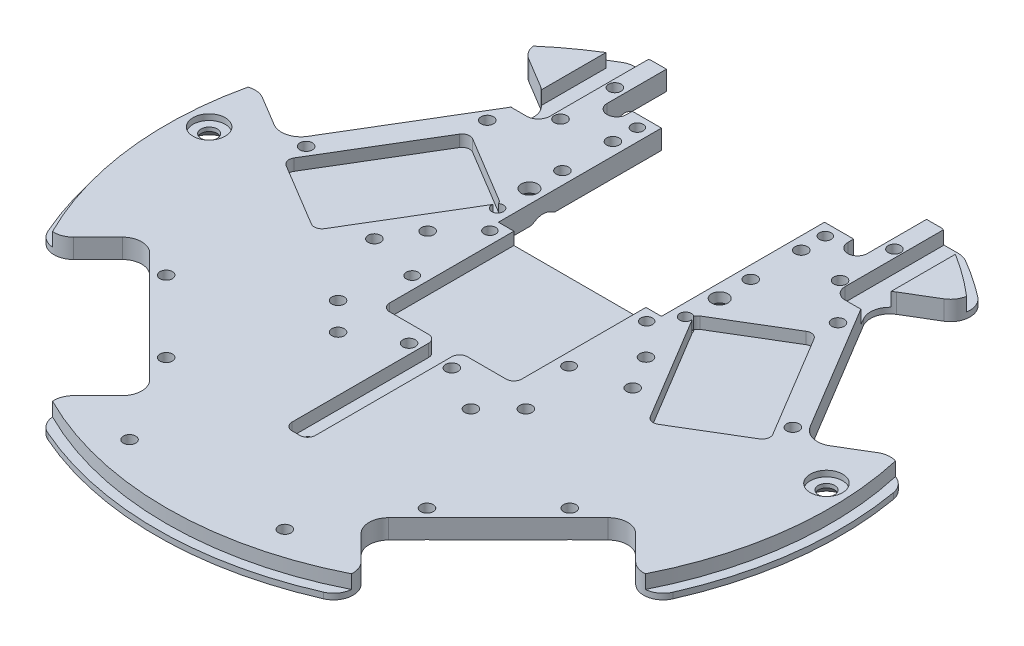
SolidWorks part; units mm, degrees
material "7079 Alloy"
ref_plane "Front" through (0, 0, 0) normal (0, 0, 1) x (1, 0, 0)
ref_plane "Top" through (0, 0, 0) normal (0, 1, 0) x (1, 0, 0)
ref_plane "Right" through (0, 0, 0) normal (1, 0, 0) x (0, 0, -1)
sketch "Sketch1" plane through (0, 0, 0) normal (0, 1, 0) x (1, 0, 0)
  line L0 (0, 0) -> (88, 0)
  line L1 (0, 88) -> (0, 0)
  line L2 (-88, 0) -> (0, 0)
  line L3 (0, -88) -> (0, 0)
  line L4 (0, 0) -> (62.2254, -62.2254)
  line L5 (0, 0) -> (-62.2254, -62.2254)
  line L6 (0, 0) -> (75.4307, 45.3234)
  line L7 (0, 0) -> (-75.4307, 45.3234)
  line L8 (59.4468, 64.8851) -> (41.5542, 54.1341)
  line L9 (41.5542, 54.1341) -> (67.3061, 11.2757)
  line L10 (67.3061, 11.2757) -> (85.1987, 22.0267)
  line L11 (77.3392, -41.9839) -> (62.579, -27.2236)
  line L12 (62.579, -27.2236) -> (27.2236, -62.579)
  line L13 (27.2236, -62.579) -> (41.9839, -77.3392)
  line L14 (-41.9839, -77.3392) -> (-27.2236, -62.579)
  line L15 (-27.2236, -62.579) -> (-62.579, -27.2236)
  line L16 (-62.579, -27.2236) -> (-77.3392, -41.9839)
  line L17 (-85.1987, 22.0267) -> (-67.3061, 11.2757)
  line L18 (-67.3061, 11.2757) -> (-41.5542, 54.1341)
  line L19 (-41.5542, 54.1341) -> (-59.4468, 64.8851)
  line L20 (-59.4468, 64.8851) -> (7.3885, 64.8851)
  line L21 (7.3885, 64.8851) -> (59.4468, 64.8851)
  line L22 (-41.5542, 54.1341) -> (0, 54.1341)
  line L23 (0, 54.1341) -> (41.5542, 54.1341)
  line L24 (41.5542, 54.1341) -> (41.5542, 77.5709)
  line L25 (-41.5542, 77.5709) -> (0, 77.5709)
  line L26 (-41.5542, 77.5709) -> (-41.5542, 54.1341)
  line L27 (0, 77.5709) -> (41.5542, 77.5709)
  circle A0 centre (0, 0) radius 88
  dimension "D1" = 176
  dimension "D2" = 31
  dimension "D3" = 31
  dimension "D4" = 45
  dimension "D5" = 24.5
  dimension "D6" = 24.5
  dimension "D7" = 24.5
  dimension "D8" = 24.5
  dimension "D9" = 25
  dimension "D10" = 25
  dimension "D11" = 25
  dimension "D12" = 25
  dimension "D13" = 25
  dimension "D14" = 25
  dimension "D15" = 25
  dimension "D16" = 25
sketch "Sketch2" plane through (0, 0, 0) normal (0, 1, 0) x (1, 0, 0)
  line L0 (85.1987, 22.0267) -> (67.3061, 11.2757)
  line L1 (67.3061, 11.2757) -> (41.5542, 54.1341)
  line L2 (77.3392, -41.9839) -> (62.579, -27.2236)
  line L3 (62.579, -27.2236) -> (27.2236, -62.579)
  line L4 (27.2236, -62.579) -> (41.9839, -77.3392)
  line L5 (-41.9839, -77.3392) -> (-27.2236, -62.579)
  line L6 (-27.2236, -62.579) -> (-62.579, -27.2236)
  line L7 (-62.579, -27.2236) -> (-77.3392, -41.9839)
  line L8 (-85.1987, 22.0267) -> (-67.3061, 11.2757)
  line L9 (-67.3061, 11.2757) -> (-41.5542, 54.1341)
  line L10 (-43, 76.7789) -> (43, 76.7789)
  line L15 (-41.5542, 54.1341) -> (-59.4468, 64.8851)
  line L16 (0, 0) -> (0, 111.6496) construction
  line L17 (41.5542, 54.1341) -> (59.4468, 64.8851)
  line L18 (-43, 76.7789) -> (43, 76.7789) construction
  arc A0 (85.1987, 22.0267) -> (77.3392, -41.9839) centre (0, 0) cw
  arc A1 (41.9839, -77.3392) -> (-41.9839, -77.3392) centre (0, 0) cw
  arc A2 (-77.3392, -41.9839) -> (-85.1987, 22.0267) centre (0, 0) cw
  arc A3 (-43, 76.7789) -> (-59.4468, 64.8851) centre (0, 0) ccw
  arc A4 (59.4468, 64.8851) -> (43, 76.7789) centre (0, 0) ccw
  dimension "D2" = 86
extrude "Extrude1" add sketch "Sketch2" against normal blind 5
sketch "Sketch3" plane through (0, 0, 0) normal (0, 1, 0) x (1, 0, 0)
  line L0 (-21, 76.7789) -> (-21, 21)
  line L1 (-21, 21) -> (21, 21)
  line L2 (21, 21) -> (21, 76.7789)
  line L3 (43, 76.7789) -> (-43, 76.7789) construction
  line L5 (-21, 76.7789) -> (21, 76.7789)
  dimension "D1" = 21
  dimension "D2" = 21
  dimension "D3" = 21
extrude "Extrude2" cut sketch "Sketch3" against normal up to surface (5 mm away) up to face at (0, -5, -1.5971)
sketch "Sketch4" plane through (0, 0, 0) normal (0, 1, 0) x (-1, 0, 0)
  line L0 (17, 13) -> (17, -27)
  line L1 (-3, 13) -> (-3, 52.119)
  line L2 (17, 13) -> (3, 13)
  line L3 (17, -27) -> (-17, -27)
  line L4 (-17, -27) -> (-17, 13)
  line L5 (21, -21) -> (-21, -21) construction
  line L6 (-3, 52.119) -> (3, 52.119)
  line L7 (3, 52.119) -> (3, 13)
  line L9 (-3, 13) -> (-17, 13)
  dimension "D1" = 34
  dimension "D2" = 17
  dimension "D3" = 34
  dimension "D4" = 40
  dimension "D5" = 6
  dimension "D6" = 14
extrude "Extrude3" cut sketch "Sketch4" against normal blind 3.2
sketch "Sketch5" plane through (0, 0, 0) normal (0, 1, 0) x (1, 0, 0)
  line L0 (42.9633, -4.5175) -> (62.6781, 7.3283)
  line L1 (62.6781, 7.3283) -> (44.6518, 37.3292)
  line L2 (44.6518, 37.3292) -> (24.9369, 25.4833)
  line L3 (24.9369, 25.4833) -> (42.9633, -4.5175)
  line L5 (67.3061, 11.2757) -> (41.5542, 54.1341) construction
  line L6 (85.1987, 22.0267) -> (67.3061, 11.2757) construction
  dimension "D1" = 6
  dimension "D2" = 35
  dimension "D3" = 23
  dimension "D4" = 1
extrude "Extrude4" cut sketch "Sketch5" against normal blind 3
mirror "Mirror1" about plane through (0, 0, 0) normal (1, 0, 0) of "Extrude4"
sketch "Sketch6" plane through (0, 0, 0) normal (0, 1, 0) x (1, 0, 0)
  line L0 (0, 0) -> (75.4307, 45.3234) construction
  line L1 (41.5542, 54.1341) -> (67.3061, 11.2757) construction
  line L2 (62.579, -27.2236) -> (27.2236, -62.579) construction
  line L3 (0, 0) -> (62.2254, -62.2254) construction
  circle A0 centre (45.1631, 42.303) radius 1.6
  circle A1 centre (62.6744, 13.1593) radius 1.6
  circle A2 centre (51.9723, -33.5876) radius 1.6
  circle A3 centre (33.5876, -51.9723) radius 1.6
  dimension "D1" = 3.2
  dimension "D2" = 3.2
  dimension "D3" = 3.2
  dimension "D4" = 3.2
  dimension "D6" = 3
  dimension "D8" = 3
  dimension "D9" = 3
  dimension "D10" = 13
  dimension "D11" = 13
  dimension "D12" = 3
  dimension "D5" = 13
  dimension "D7" = 21
extrude "Extrude5" cut sketch "Sketch6" against normal up to surface (5 mm away) up to face at (0, -5, -10.1957)
mirror "Mirror2" about plane through (0, 0, 0) normal (1, 0, 0) of "Extrude5"
sketch "Sketch7" plane through (0, 0, 0) normal (0, 1, 0) x (-1, 0, 0)
  line L1 (-21, -21) -> (-21, -76.7789) construction
  line L2 (-17, -21) -> (-21, -21) construction
  circle A0 centre (-24.2, -60) radius 1.5
  circle A1 centre (-24.2, -24) radius 1.5
  dimension "D2" = 3.2
  dimension "D3" = 3
  dimension "D4" = 3
  dimension "D5" = 3.2
  dimension "D6" = 3
  dimension "D1" = 36
extrude "Extrude6" cut sketch "Sketch7" against normal up to surface (5 mm away) up to face at (-51.9723, -5, 31.9876)
mirror "Mirror3" about plane through (0, 0, 0) normal (1, 0, 0) of "Extrude6"
sketch "Sketch8" plane through (0, 0, 0) normal (0, 1, 0) x (1, 0, 0)
  line L0 (33.5, 68.7344) -> (33.5, 63)
  line L6 (33.5, 63) -> (21, 63)
  line L7 (21, 21) -> (21, 76.7789) construction
  line L8 (21, 63) -> (21, 76.7789)
  line L9 (21, 76.7789) -> (33.5, 76.7789)
  line L10 (43, 76.7789) -> (21, 76.7789) construction
  line L11 (33.5, 76.7789) -> (33.5, 68.7344)
  circle A0 centre (24.2, 60) radius 1.5 construction
  dimension "D4" = 3
extrude "Extrude7" cut sketch "Sketch8" against normal up to surface (5 mm away) up to face at (-24.2, -5, -61.5)
mirror "Mirror4" about plane through (0, 0, 0) normal (1, 0, 0) of "Extrude7"
sketch "Sketch9" plane through (0, 0, 0) normal (0, 1, 0) x (1, 0, 0)
  line L5 (33.5, 63) -> (33.5, 76.7789) construction
  circle A0 centre (36, 66) radius 1.6
  circle A1 centre (36, 52) radius 1.6
  dimension "D1" = 3.2
  dimension "D2" = 3.2
  dimension "D3" = 52
  dimension "D4" = 66
  dimension "D5" = 2.5
extrude "Extrude8" cut sketch "Sketch9" against normal up to surface (5 mm away) up to face at (-24.2, -5, -61.5)
mirror "Mirror5" about plane through (0, 0, 0) normal (1, 0, 0) of "Extrude8"
fillet "Fillet2" radius 2 14 edges at (-17, -1.6, 13) (-42.9633, -1.5, 4.5175) (-24.9369, -1.5, -25.4833) (-44.6518, -1.5, -37.3292) (-62.6781, -1.5, -7.3283) (42.9633, -1.5, 4.5175) (24.9369, -1.5, -25.4833) (44.6518, -1.5, -37.3292) (62.6781, -1.5, -7.3283) (-3, -1.6, 52.119) (3, -1.6, 52.119) (-3, -1.6, 13) (3, -1.6, 13) (17, -1.6, 13)
fillet "Fillet3" radius 5 16 edges at (59.4468, -2.5, -64.8851) (41.5542, -2.5, -54.1341) (67.3061, -2.5, -11.2757) (85.1987, -2.5, -22.0267) (77.3392, -2.5, 41.9839) (62.579, -2.5, 27.2236) (27.2236, -2.5, 62.579) (41.9839, -2.5, 77.3392) (-27.2236, -2.5, 62.579) (-41.9839, -2.5, 77.3392) (-62.579, -2.5, 27.2236) (-77.3392, -2.5, 41.9839) (-85.1987, -2.5, -22.0267) (-67.3061, -2.5, -11.2757) (-41.5542, -2.5, -54.1341) (-59.4468, -2.5, -64.8851)
fillet "Fillet4" radius 5 2 edges at (43, -2.5, -76.7789) (-43, -2.5, -76.7789)
sketch "Sketch11" plane through (0, 0, 0) normal (0, 1, 0) x (1, 0, 0)
  line L0 (-21, 63) -> (-33.5, 63) construction
  line L3 (-21, 21) -> (-21, 63) construction
  line L4 (21, 21) -> (21, 63) construction
  circle A2 centre (24.5, 32.5) radius 2.1
  circle A3 centre (-24.5, 32.5) radius 2.1
  dimension "D2" = 30.5
  dimension "D7" = 4.2
  dimension "D8" = 4.2
  dimension "D9" = 3.5
  dimension "D10" = 3.5
extrude "Extrude10" cut sketch "Sketch11" against normal up to surface (5 mm away) up to face at (-36, -5, -67.6)
sketch "Sketch14" plane through (0, 0, 0) normal (0, 1, 0) x (1, 0, 0)
  line L3 (17.112, -24.1831) -> (24.1831, -17.112) construction
  line L4 (33.9018, -69.2571) -> (69.2571, -33.9018) construction
  line L8 (37.0444, -72.3997) -> (30.7591, -66.1145) construction
  line L9 (66.1145, -30.7591) -> (72.3997, -37.0444) construction
  line L10 (62.6744, 13.1593) -> (45.1631, 42.303) construction
  line L11 (49.6495, 58.9983) -> (75.4014, 16.1399) construction
  line L12 (45.84, 56.7093) -> (53.4591, 61.2873) construction
  line L13 (79.211, 18.4289) -> (71.5919, 13.8509) construction
  line L14 (33.5876, -51.9723) -> (51.9723, -33.5876) construction
  circle A2 centre (24.1831, -17.112) radius 1.6
  circle A3 centre (17.112, -24.1831) radius 1.6
  circle A4 centre (28.1195, 9.8961) radius 1.6
  circle A5 centre (33.2699, 1.3244) radius 1.6
  point P28 (20.6475, -20.6475)
  dimension "D3" = 3.2
  dimension "D4" = 31.3
  dimension "D7" = 31.3
  dimension "D9" = 3.2
  dimension "D10" = 31.3
  dimension "D12" = 10
  dimension "D8" = 3.2
  dimension "D14" = 3.2
  dimension "D2" = 10
  dimension "D5" = 31.3
  dimension "D6" = 19
  dimension "D13" = 25
sketch "Sketch27" plane through (0, 0, 0) normal (0, 1, 0) x (1, 0, 0)
  line L0 (-17, 21) -> (-17, -11) construction
  line L1 (17, 21) -> (21, 21) construction
  line L2 (17, -11) -> (17, 21) construction
  line L3 (-17, 21) -> (-17, -11) construction
  line L4 (0, -7.044) -> (0, 19.6641) construction
  circle A0 centre (20.2, 18) radius 1.5
  circle A1 centre (-20.2, 18) radius 1.5
  circle A2 centre (-20.2, -2) radius 1.5311
  circle A3 centre (20.2, -2) radius 1.5311
  dimension "D1" = 3
  dimension "D2" = 3
  dimension "D4" = 3.2
  dimension "D3" = 3
  dimension "D5" = 3.2
  dimension "D6" = 3.2
  dimension "D7" = 20
extrude "Extrude26" cut sketch "Sketch27" against normal up to surface (5 mm away) up to face at (-24.5, -5, -34.6)
sketch "Sketch29" plane through (0, 0, 0) normal (0, 1, 0) x (1, 0, 0)
  circle A0 centre (-79.5, 5) radius 4.15
  circle A1 centre (79.5, 5) radius 4.15
  dimension "D2" = 79.5
  dimension "D4" = 8.3
  dimension "D5" = 8.3
  dimension "D1" = 5
  dimension "D3" = 79.5
extrude "Extrude28" cut sketch "Sketch29" against normal blind 1.5
sketch "Sketch30" plane through (0, -1.5, 0) normal (0, 1, 0) x (1, 0, 0)
  circle A0 centre (79.5, 5) radius 2.1
  circle A1 centre (-79.5, 5) radius 2.1
  dimension "D1" = 4.2
  dimension "D2" = 4.2
extrude "Extrude29" cut sketch "Sketch30" against normal up to surface (3.5 mm away) up to face at (20.2, -5, 0.4689)
extrude "Extrude30" cut sketch "Sketch14" against normal up to surface (5 mm away) up to face at (-79.5, -5, -7.1)
mirror "Mirror9" about plane through (0, 0, 0) normal (1, 0, 0) of "Extrude30"
sketch "Sketch31" plane through (0, 0, 0) normal (0, 1, 0) x (1, 0, 0)
  line L0 (-29.5846, 80.2185) -> (-30.4496, 82.564)
  line L2 (28.2614, 80.6941) -> (28.0948, 83.3947)
  arc A0 (-29.5846, 80.2185) -> (28.2614, 80.6941) centre (0, 0) ccw
  arc A1 (-30.4496, 82.564) -> (28.0948, 83.3947) centre (0, 0) ccw
  dimension "D1" = 171
  dimension "D2" = 88
extrude "Cut-Extrude1" cut sketch "Sketch31" against normal blind 3.5
sketch "Sketch33" plane through (0, 0, 0) normal (0, 1, 0) x (1, 0, 0)
  line L0 (-38, 76.7789) -> (-45, 76.7789)
  line L3 (-33.5, 76.7789) -> (-37.6198, 76.7789) construction
  line L4 (-45, 76.7789) -> (-45, 48.2789)
  line L9 (-45, 48.2789) -> (-38, 48.2789)
  line L10 (-38, 48.2789) -> (-38, 76.7789)
  line L11 (0, 0) -> (0, 104.2822) construction
  line L12 (38, 48.2789) -> (38, 76.7789)
  line L13 (45, 48.2789) -> (38, 48.2789)
  line L14 (45, 76.7789) -> (45, 48.2789)
  line L15 (38, 76.7789) -> (45, 76.7789)
  dimension "D1" = 4.5
  dimension "D2" = 7
  dimension "D3" = 28.5
extrude "Cut-Extrude3" cut sketch "Sketch33" against normal blind 3.5
fillet "Fillet5" radius 3 2 edges at (38, -1.75, -48.2789) (-38, -1.75, -48.2789)
sketch "Sketch34" plane through (0, 0, 0) normal (0, 1, 0) x (1, 0, 0)
  line L0 (-33.5, 63) -> (-33.5, 59)
  line L1 (-33.5, 59) -> (-28.5, 59)
  line L2 (-28.5, 59) -> (-28.5, 63)
  line L4 (-21, 63) -> (-33.5, 63) construction
  line L5 (-28.5, 63) -> (-33.5, 63)
  line L6 (0, 0) -> (0, 90.7879) construction
  line L7 (28.5, 63) -> (33.5, 63)
  line L8 (28.5, 59) -> (28.5, 63)
  line L9 (33.5, 59) -> (28.5, 59)
  line L10 (33.5, 63) -> (33.5, 59)
  dimension "D1" = 4
  dimension "D2" = 5
extrude "Cut-Extrude4" cut sketch "Sketch34" against normal blind 10
fillet "Fillet6" radius 2.5 4 edges at (28.5, -2.5, -59) (33.5, -2.5, -59) (-28.5, -2.5, -59) (-33.5, -2.5, -59)
sketch "Sketch37" plane through (0, 0, 0) normal (0, 1, 0) x (1, 0, 0)
  line L1 (-5.5, -17.5) -> (5.5, -17.5) construction
  line L2 (-24.5, 32.5) -> (24.5, 32.5) construction
  line L3 (0, 0) -> (0, -85.5) construction
  circle A0 centre (-5.5, -17.5) radius 1.6
  circle A1 centre (5.5, -17.5) radius 1.6
  arc A5 (-38.492, -76.3454) -> (38.492, -76.3454) centre (0, 0) ccw construction
  dimension "D1" = 3.2
  dimension "D2" = 3.2
  dimension "D3" = 11
  dimension "D4" = 50
  dimension "D5" = 5.5
extrude "Cut-Extrude7" cut sketch "Sketch37" against normal blind 10
sketch "Sketch38" plane through (0, -3.2, 0) normal (0, 1, 0) x (1, 0, 0)
  line L0 (3, -50.119) -> (3, -15) construction
  circle A0 centre (0, -49) radius 1.25
  dimension "D3" = 2.5
  dimension "D1" = 49
  dimension "D2" = 3
extrude "Cut-Extrude8" cut sketch "Sketch38" against normal blind 10
sketch "Sketch39" plane through (0, 0, 0) normal (0, 1, 0) x (1, 0, 0)
  line L0 (-21, 63) -> (-28.5, 63) construction
  line L1 (-21, 63) -> (-21, 21) construction
  line L2 (0, 0) -> (0, 77.617) construction
  circle A0 centre (-24.25, 53.75) radius 1.6
  circle A1 centre (-24.25, 40.75) radius 1.6
  circle A2 centre (24.25, 40.75) radius 1.6
  circle A3 centre (24.25, 53.75) radius 1.6
  dimension "D2" = 3.2
  dimension "D5" = 3.2
  dimension "D1" = 9.25
  dimension "D3" = 3.25
  dimension "D4" = 3.25
  dimension "D6" = 13
extrude "Cut-Extrude9" cut sketch "Sketch39" against normal blind 10
sketch "Sketch44" plane through (0, 0, 0) normal (0, 1, 0) x (1, 0, 0)
  line L2 (0, 0) -> (0, -75) construction
  circle A0 centre (-20, -75) radius 1.6
  circle A1 centre (20, -75) radius 1.6
  dimension "D1" = 3.2
  dimension "D2" = 20
  dimension "D3" = 75
extrude "Cut-Extrude10" cut sketch "Sketch44" against normal blind 60
chamfer "Chamfer1" distance 1.5 angle 45 36 edges at (-5.5, -5, 15.9) (5.5, -5, 15.9) (-36, -5, -53.6) (-36, -5, -67.6) (-24.2, -5, -61.5) (36, -5, -53.6) (36, -5, -67.6) (24.2, -5, -61.5) (-24.2, -5, -25.5) (24.2, -5, -25.5) (-20.2, -5, -19.5) (20.2, -5, -19.5) (-33.2699, -5, -2.9244) (-24.1831, -5, 15.512) (-17.112, -5, 22.5831) (17.112, -5, 22.5831) (28.1195, -5, -11.4961) (33.2699, -5, -2.9244) (-45.1631, -5, -43.903) (-62.6744, -5, -14.7593) (45.1631, -5, -43.903) (62.6744, -5, -14.7593) (51.9723, -5, 31.9876) (33.5876, -5, 50.3723) (-33.5876, -5, 50.3723) (-51.9723, -5, 31.9876) (-28.1195, -5, -11.4961) (24.1831, -5, 15.512) (-24.25, -5, -42.35) (-24.25, -5, -55.35) (24.25, -5, -42.35) (24.25, -5, -55.35) (-20.2, -5, 0.4689) (20.2, -5, 0.4689) (-20, -5, 73.4) (20, -5, 73.4)
chamfer "Chamfer2" distance 2.5 angle 45 4 edges at (79.5, -5, -7.1) (-24.5, -5, -34.6) (24.5, -5, -34.6) (-79.5, -5, -7.1)
